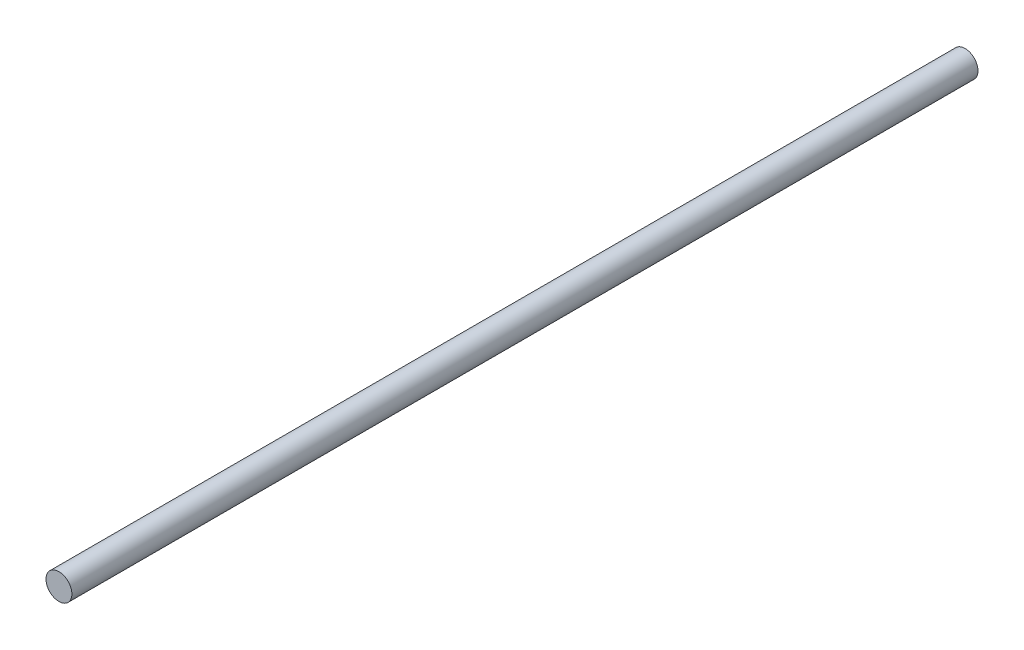
SolidWorks part; units mm, degrees
ref_plane "Front Plane" through (0, 0, 0) normal (0, 0, 1) x (1, 0, 0)
ref_plane "Top Plane" through (0, 0, 0) normal (0, 1, 0) x (1, 0, 0)
ref_plane "Right Plane" through (0, 0, 0) normal (1, 0, 0) x (0, 0, -1)
sketch "Sketch1" plane through (0, 0, 0) normal (0, 0, 1) x (1, 0, 0)
  circle A0 centre (0, 0) radius 4
  dimension "D1" = 8
extrude "Boss-Extrude1" add sketch "Sketch1" along normal blind 140 and the other way blind 140
